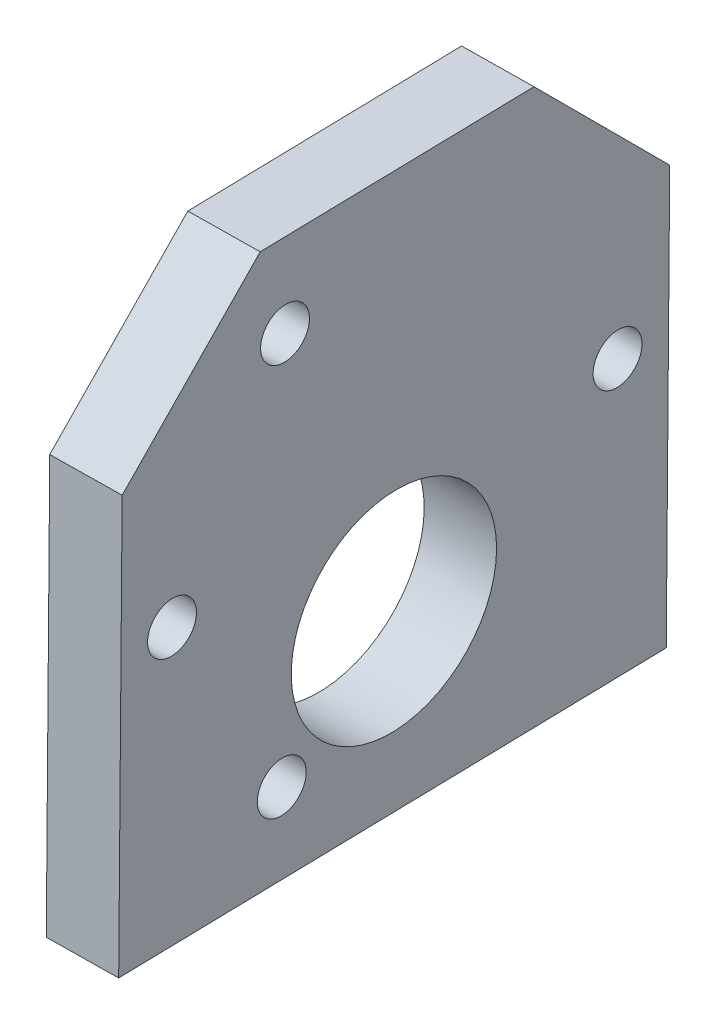
SolidWorks part; units mm, degrees
material "1060 Alloy"
ref_plane "Front" through (0, 0, 0) normal (0, 0, 1) x (1, 0, 0)
ref_plane "Top" through (0, 0, 0) normal (0, 1, 0) x (1, 0, 0)
ref_plane "Right" through (0, 0, 0) normal (1, 0, 0) x (0, 0, -1)
sketch "Sketch1" plane through (39.5296, -0.3237, -0.8516) normal (0.9997, -0.0082, -0.0215) x (-0.0215, 0.0001, -0.9998)
  line L1 (-19.05, 19.05) -> (19.05, 19.05)
  line L2 (-19.05, 19.05) -> (-19.05, -19.05)
  line L3 (-19.05, -19.05) -> (19.05, -19.05)
  line L4 (19.05, 19.05) -> (19.05, -19.05)
  line L5 (0, 19.05) -> (0, -19.05) construction
  circle A6 centre (0, -7.112) radius 7.1438
  point P4 (0, 0)
  dimension "D4" = 14.2875
  dimension "D5" = 7.112
  dimension "D1" = 38.1
  dimension "D2" = 19.05
  dimension "D3" = 19.05
extrude "Boss-Extrude1" add sketch "Sketch1" along normal blind 4.826
chamfer "Chamfer1" distance 9.525 angle 45 2 edges at (41.6877, 18.7076, -19.9509) (42.5083, 18.7042, 18.1403)
hole_wizard "M3 Clearance Hole1" positions "Sketch2" profile "Sketch3" hole size "M3" standard "ANSI Metric" end condition through all
sketch "Sketch2" plane through (44.3544, -0.3632, -0.9556) normal (0.9997, -0.0082, -0.0215) x (-0.0215, 0.0001, -0.9998)
  point P5 (15.5, -0.112)
  point P8 (-15.5, -0.112)
  point P11 (-7.75, -13.5354)
  point P14 (-7.75, 13.3114)
sketch "Sketch3" plane through (44.0196, -0.4739, -16.452) normal (0.021, 0.707, 0.707) x (-0.0094, 0.7072, -0.7069)
  line L0 (0, 0) -> (0, 5.9583)
  line L1 (0, 5.9583) -> (1.7, 5.9583)
  line L2 (1.7, 5.9583) -> (1.7, 0)
  line L5 (1.7, 0) -> (0, 0)
  line L11 (0, -6.35) -> (0, 107.95) construction
  dimension "Thru Hole Dia." = 3.4
  dimension "Thru Hole Depth" = 5.9583
